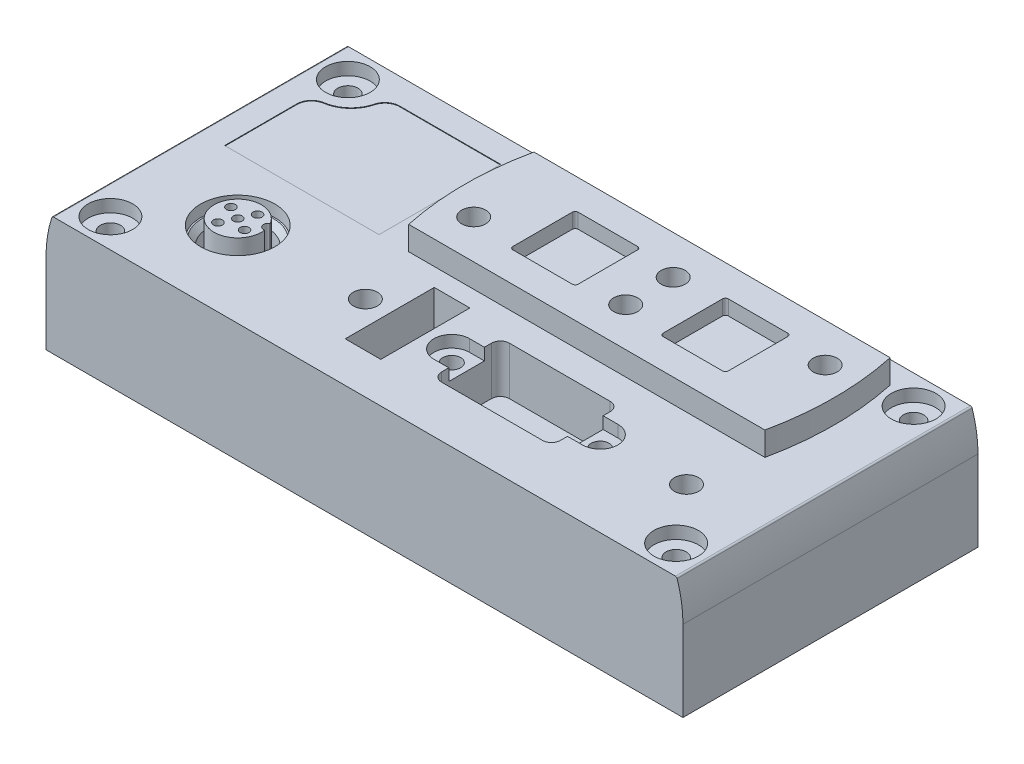
SolidWorks part; units mm, degrees
ref_plane "Front Plane" through (0, 0, 0) normal (0, 0, 1) x (1, 0, 0)
ref_plane "Top Plane" through (0, 0, 0) normal (0, 1, 0) x (1, 0, 0)
ref_plane "Right Plane" through (0, 0, 0) normal (1, 0, 0) x (0, 0, -1)
ref_plane "Plane1" through (0, 0, 0) normal (0, 0, 1) x (1, 0, 0)
sketch "Sketch1" plane through (0, 0, 0) normal (0, 0, 1) x (1, 0, 0)
  line L0 (-53.65, 13.6) -> (-53.65, 0)
  line L1 (-53.65, 0) -> (53.65, 0)
  line L2 (53.65, 0) -> (53.65, 13.6)
  line L3 (52.3818, 20) -> (-52.3818, 20)
  arc A0 (53.65, 13.6) -> (52.667, 19.7929) centre (33.65, 13.6) ccw
  arc A1 (52.667, 19.7929) -> (52.3818, 20) centre (52.3818, 19.7) ccw
  arc A2 (-52.3818, 20) -> (-52.667, 19.7929) centre (-52.3818, 19.7) ccw
  arc A3 (-52.667, 19.7929) -> (-53.65, 13.6) centre (-33.65, 13.6) ccw
extrude "Boss-Extrude1" add sketch "Sketch1" against normal blind 24.85 and the other way blind 24.85
ref_plane "Plane2" through (0, 0, 20) normal (0, 0, 1) x (1, 0, 0)
sketch "Sketch2" plane through (0, 0, 20) normal (0, 0, 1) x (1, 0, 0)
  line L0 (47.65, 20) -> (51.4, 20)
  line L1 (51.4, 20) -> (51.4, 17.9)
  line L2 (51.4, 17.9) -> (49.35, 17.9)
  line L3 (49.35, 17.9) -> (49.35, 12.7732)
  line L4 (49.35, 12.7732) -> (49.05, 12.6)
  line L5 (49.05, 12.6) -> (49.05, 12)
  line L6 (49.05, 12) -> (49.35, 12)
  line L7 (49.35, 12) -> (49.35, 0)
  line L8 (49.35, 0) -> (47.65, 0)
  line L9 (47.65, 0) -> (47.65, 20)
  line L10 (47.65, 0) -> (47.65, 20) construction
revolve "Cut-Revolve1" cut sketch "Sketch2" angle 360 about L10 reverse direction yes
ref_plane "Plane3" through (0, 0, -20) normal (0, 0, 1) x (1, 0, 0)
sketch "Sketch3" plane through (0, 0, -20) normal (0, 0, 1) x (1, 0, 0)
  line L0 (47.65, 20) -> (51.4, 20)
  line L1 (51.4, 20) -> (51.4, 17.9)
  line L2 (51.4, 17.9) -> (49.35, 17.9)
  line L3 (49.35, 17.9) -> (49.35, 12.7732)
  line L4 (49.35, 12.7732) -> (49.05, 12.6)
  line L5 (49.05, 12.6) -> (49.05, 12)
  line L6 (49.05, 12) -> (49.35, 12)
  line L7 (49.35, 12) -> (49.35, 0)
  line L8 (49.35, 0) -> (47.65, 0)
  line L9 (47.65, 0) -> (47.65, 20)
  line L10 (47.65, 0) -> (47.65, 20) construction
revolve "Cut-Revolve2" cut sketch "Sketch3" angle 360 about L10 reverse direction yes
ref_plane "Plane4" through (0, 0, -20) normal (0, 0, 1) x (1, 0, 0)
sketch "Sketch4" plane through (0, 0, -20) normal (0, 0, 1) x (1, 0, 0)
  line L0 (-47.65, 20) -> (-43.9, 20)
  line L1 (-43.9, 20) -> (-43.9, 17.9)
  line L2 (-43.9, 17.9) -> (-45.95, 17.9)
  line L3 (-45.95, 17.9) -> (-45.95, 12.7732)
  line L4 (-45.95, 12.7732) -> (-46.25, 12.6)
  line L5 (-46.25, 12.6) -> (-46.25, 12)
  line L6 (-46.25, 12) -> (-45.95, 12)
  line L7 (-45.95, 12) -> (-45.95, 0)
  line L8 (-45.95, 0) -> (-47.65, 0)
  line L9 (-47.65, 0) -> (-47.65, 20)
  line L10 (-47.65, 0) -> (-47.65, 20) construction
revolve "Cut-Revolve3" cut sketch "Sketch4" angle 360 about L10 reverse direction yes
ref_plane "Plane5" through (0, 0, 20) normal (0, 0, 1) x (1, 0, 0)
sketch "Sketch5" plane through (0, 0, 20) normal (0, 0, 1) x (1, 0, 0)
  line L0 (-47.65, 20) -> (-43.9, 20)
  line L1 (-43.9, 20) -> (-43.9, 17.9)
  line L2 (-43.9, 17.9) -> (-45.95, 17.9)
  line L3 (-45.95, 17.9) -> (-45.95, 12.7732)
  line L4 (-45.95, 12.7732) -> (-46.25, 12.6)
  line L5 (-46.25, 12.6) -> (-46.25, 12)
  line L6 (-46.25, 12) -> (-45.95, 12)
  line L7 (-45.95, 12) -> (-45.95, 0)
  line L8 (-45.95, 0) -> (-47.65, 0)
  line L9 (-47.65, 0) -> (-47.65, 20)
  line L10 (-47.65, 0) -> (-47.65, 20) construction
revolve "Cut-Revolve4" cut sketch "Sketch5" angle 360 about L10 reverse direction yes
ref_plane "Plane6" through (0, 0, 10.55) normal (0, 0, 1) x (1, 0, 0)
sketch "Sketch6" plane through (0, 0, 10.55) normal (0, 0, 1) x (1, 0, 0)
  line L0 (-35.65, 12.4) -> (-41.65, 12.4)
  line L1 (-41.65, 12.4) -> (-40.703, 13.347)
  line L2 (-40.703, 13.347) -> (-40.703, 17.053)
  line L3 (-40.703, 17.053) -> (-41.65, 18)
  line L4 (-41.65, 18) -> (-41.9, 18)
  line L5 (-41.9, 18) -> (-41.9, 20)
  line L6 (-41.9, 20) -> (-35.65, 20)
  line L7 (-35.65, 20) -> (-35.65, 12.4)
  line L8 (-35.65, 20) -> (-35.65, 12.4) construction
revolve "Cut-Revolve5" cut sketch "Sketch6" angle 360 about L8 reverse direction yes
cosmetic thread "Cosmetic Thread1" parameters "D1"=5.6, "D2"=12
ref_plane "Plane7" through (0, 21, 0) normal (0, 1, 0) x (1, 0, 0)
sketch "Sketch7" plane through (0, 21, 0) normal (0, 1, 0) x (1, 0, 0)
  arc A0 (-32.1775, -8.5646) -> (-31.6913, -9.9766) centre (-35.65, -10.55) ccw
  arc A1 (-31.6913, -9.9766) -> (-32.1775, -8.5646) centre (-31.8679, -9.2477) cw
  circle A2 centre (-33.403, -11.6459) radius 0.75
  circle A3 centre (-34.5541, -8.303) radius 0.75
  circle A4 centre (-35.65, -10.55) radius 0.75
  circle A5 centre (-36.7459, -12.797) radius 0.75
  circle A6 centre (-37.897, -9.4541) radius 0.75
extrude "Boss-Extrude2" add sketch "Sketch7" against normal blind 8.6
ref_plane "Plane8" through (0, 24, 0) normal (0, 1, 0) x (1, 0, 0)
sketch "Sketch8" plane through (0, 24, 0) normal (0, 1, 0) x (1, 0, 0)
  line L0 (-17.4, 0) -> (42.6, 0)
  line L1 (42.6, 21.1) -> (-17.4, 21.1)
  arc A0 (-17.4, 21.1) -> (-17.4, 0) centre (31.4743, 10.55) ccw
  arc A1 (42.6, 0) -> (42.6, 21.1) centre (-6.2743, 10.55) ccw
extrude "Boss-Extrude3" add sketch "Sketch8" against normal blind 4
ref_plane "Plane9" through (0, 24, 0) normal (0, 1, 0) x (1, 0, 0)
sketch "Sketch9" plane through (0, 24, 0) normal (0, 1, 0) x (1, 0, 0)
  circle A0 centre (-13, 6.55) radius 2.025
extrude "Cut-Extrude1" cut sketch "Sketch9" against normal blind 6.6
ref_plane "Plane10" through (0, 24, 0) normal (0, 1, 0) x (1, 0, 0)
sketch "Sketch10" plane through (0, 24, 0) normal (0, 1, 0) x (1, 0, 0)
  circle A0 centre (12.6, 14.55) radius 2.025
extrude "Cut-Extrude2" cut sketch "Sketch10" against normal blind 6.6
ref_plane "Plane11" through (0, 24, 0) normal (0, 1, 0) x (1, 0, 0)
sketch "Sketch11" plane through (0, 24, 0) normal (0, 1, 0) x (1, 0, 0)
  circle A0 centre (12.6, 6.55) radius 2.025
extrude "Cut-Extrude3" cut sketch "Sketch11" against normal blind 6.6
ref_plane "Plane12" through (0, 24, 0) normal (0, 1, 0) x (1, 0, 0)
sketch "Sketch12" plane through (0, 24, 0) normal (0, 1, 0) x (1, 0, 0)
  circle A0 centre (38.2, 14.55) radius 2.025
extrude "Cut-Extrude4" cut sketch "Sketch12" against normal blind 6.6
ref_plane "Plane13" through (0, 20, 0) normal (0, 1, 0) x (1, 0, 0)
sketch "Sketch13" plane through (0, 20, 0) normal (0, 1, 0) x (1, 0, 0)
  circle A0 centre (-14.15, -10.55) radius 2.025
extrude "Cut-Extrude5" cut sketch "Sketch13" against normal blind 6.6
ref_plane "Plane14" through (0, 20, 0) normal (0, 1, 0) x (1, 0, 0)
sketch "Sketch14" plane through (0, 20, 0) normal (0, 1, 0) x (1, 0, 0)
  circle A0 centre (39.95, -10.55) radius 2.025
extrude "Cut-Extrude6" cut sketch "Sketch14" against normal blind 6.6
ref_plane "Plane15" through (0, 20, 0) normal (0, 1, 0) x (1, 0, 0)
sketch "Sketch15" plane through (0, 20, 0) normal (0, 1, 0) x (1, 0, 0)
  line L0 (0.4, -13.55) -> (2.9, -13.55)
  line L1 (2.9, -13.55) -> (2.9, -14.55)
  line L2 (3.9, -15.55) -> (21.9, -15.55)
  line L3 (22.9, -14.55) -> (22.9, -13.55)
  line L4 (22.9, -13.55) -> (25.4, -13.55)
  line L5 (25.4, -7.55) -> (22.9, -7.55)
  line L6 (22.9, -7.55) -> (22.9, -6.55)
  line L7 (21.9, -5.55) -> (3.9, -5.55)
  line L8 (2.9, -6.55) -> (2.9, -7.55)
  line L9 (2.9, -7.55) -> (0.4, -7.55)
  arc A0 (0.4, -7.55) -> (0.4, -13.55) centre (0.4, -10.55) ccw
  arc A1 (2.9, -14.55) -> (3.9, -15.55) centre (3.9, -14.55) ccw
  arc A2 (21.9, -15.55) -> (22.9, -14.55) centre (21.9, -14.55) ccw
  arc A3 (25.4, -13.55) -> (25.4, -7.55) centre (25.4, -10.55) ccw
  arc A4 (22.9, -6.55) -> (21.9, -5.55) centre (21.9, -6.55) ccw
  arc A5 (3.9, -5.55) -> (2.9, -6.55) centre (3.9, -6.55) ccw
extrude "Cut-Extrude7" cut sketch "Sketch15" against normal blind 2
ref_plane "Plane16" through (0, 20, 0) normal (0, 1, 0) x (1, 0, 0)
sketch "Sketch16" plane through (0, 20, 0) normal (0, 1, 0) x (1, 0, 0)
  line L0 (2.9, -6.35) -> (2.9, -14.75)
  line L1 (4.4, -16.25) -> (21.4, -16.25)
  line L2 (22.9, -14.75) -> (22.9, -6.35)
  line L3 (21.4, -4.85) -> (4.4, -4.85)
  arc A0 (2.9, -14.75) -> (4.4, -16.25) centre (4.4, -14.75) ccw
  arc A1 (21.4, -16.25) -> (22.9, -14.75) centre (21.4, -14.75) ccw
  arc A2 (22.9, -6.35) -> (21.4, -4.85) centre (21.4, -6.35) ccw
  arc A3 (4.4, -4.85) -> (2.9, -6.35) centre (4.4, -6.35) ccw
extrude "Cut-Extrude8" cut sketch "Sketch16" against normal blind 8.1
ref_plane "Plane17" through (0, 20, 0) normal (0, 1, 0) x (1, 0, 0)
sketch "Sketch17" plane through (0, 20, 0) normal (0, 1, 0) x (1, 0, 0)
  circle A0 centre (25.4, -10.55) radius 1.5
extrude "Cut-Extrude9" cut sketch "Sketch17" against normal blind 5
ref_plane "Plane18" through (0, 20, 0) normal (0, 1, 0) x (1, 0, 0)
sketch "Sketch18" plane through (0, 20, 0) normal (0, 1, 0) x (1, 0, 0)
  circle A0 centre (0.4, -10.55) radius 1.5
extrude "Cut-Extrude10" cut sketch "Sketch18" against normal blind 5
ref_plane "Plane19" through (0, 24, 0) normal (0, 1, 0) x (1, 0, 0)
sketch "Sketch19" plane through (0, 24, 0) normal (0, 1, 0) x (1, 0, 0)
  line L0 (-5.4, 15.55) -> (-5.4, 5.55)
  line L1 (-4.9, 5.05) -> (5.1, 5.05)
  line L2 (5.6, 5.55) -> (5.6, 15.55)
  line L3 (5.1, 16.05) -> (-4.9, 16.05)
  arc A0 (-5.4, 5.55) -> (-4.9, 5.05) centre (-4.9, 5.55) ccw
  arc A1 (5.1, 5.05) -> (5.6, 5.55) centre (5.1, 5.55) ccw
  arc A2 (5.6, 15.55) -> (5.1, 16.05) centre (5.1, 15.55) ccw
  arc A3 (-4.9, 16.05) -> (-5.4, 15.55) centre (-4.9, 15.55) ccw
extrude "Cut-Extrude11" cut sketch "Sketch19" against normal blind 2.5
ref_plane "Plane20" through (0, 24, 0) normal (0, 1, 0) x (1, 0, 0)
sketch "Sketch20" plane through (0, 24, 0) normal (0, 1, 0) x (1, 0, 0)
  line L0 (19.9, 15.55) -> (19.9, 5.55)
  line L1 (20.4, 5.05) -> (30.4, 5.05)
  line L2 (30.9, 5.55) -> (30.9, 15.55)
  line L3 (30.4, 16.05) -> (20.4, 16.05)
  arc A0 (19.9, 5.55) -> (20.4, 5.05) centre (20.4, 5.55) ccw
  arc A1 (30.4, 5.05) -> (30.9, 5.55) centre (30.4, 5.55) ccw
  arc A2 (30.9, 15.55) -> (30.4, 16.05) centre (30.4, 15.55) ccw
  arc A3 (20.4, 16.05) -> (19.9, 15.55) centre (20.4, 15.55) ccw
extrude "Cut-Extrude12" cut sketch "Sketch20" against normal blind 2.5
ref_plane "Plane21" through (-10.05, 0, 0) normal (1, 0, 0) x (0, 0, -1)
sketch "Sketch21" plane through (-10.05, 0, 0) normal (1, 0, 0) x (0, 0, -1)
  line L0 (-18.05, 11.9) -> (-11.05, 11.9)
  line L1 (-11.05, 11.9) -> (-11.05, 12.9)
  line L2 (-11.05, 12.9) -> (-10.05, 12.9)
  line L3 (-10.05, 12.9) -> (-10.05, 11.9)
  line L4 (-10.05, 11.9) -> (-3.05, 11.9)
  line L5 (-3.05, 11.9) -> (-3.05, 20)
  line L6 (-3.05, 20) -> (-18.05, 20)
  line L7 (-18.05, 20) -> (-18.05, 11.9)
extrude "Cut-Extrude13" cut sketch "Sketch21" along normal blind 6
ref_plane "Plane22" through (0, 0, 0) normal (0, 1, 0) x (1, 0, 0)
sketch "Sketch22" plane through (0, 0, 0) normal (0, 1, 0) x (1, 0, 0)
  line L0 (-48.4, 12.1512) -> (-48.4, -12.1512)
  line L1 (-39.4234, -20.5) -> (40.208, -20.5)
  line L2 (48.4, -12.0497) -> (48.4, 12.0497)
  line L3 (40.208, 20.5) -> (-39.4234, 20.5)
  arc A0 (-48.4, -12.1512) -> (-46.2863, -14.6126) centre (-45.91, -12.1512) ccw
  arc A1 (-46.2863, -14.6126) -> (-41.8339, -18.6341) centre (-47.11, -20) cw
  arc A2 (-41.8339, -18.6341) -> (-39.4234, -20.5) centre (-39.4234, -18.01) ccw
  arc A3 (40.208, -20.5) -> (42.0607, -18.9391) centre (40.208, -18.62) ccw
  arc A4 (42.0607, -18.9391) -> (46.9131, -13.8882) centre (48.22, -20) cw
  arc A5 (46.9131, -13.8882) -> (48.4, -12.0497) centre (46.52, -12.0497) ccw
  arc A6 (48.4, 12.0497) -> (46.9131, 13.8882) centre (46.52, 12.0497) ccw
  arc A7 (46.9131, 13.8882) -> (42.0607, 18.9391) centre (48.22, 20) cw
  arc A8 (42.0607, 18.9391) -> (40.208, 20.5) centre (40.208, 18.62) ccw
  arc A9 (-39.4234, 20.5) -> (-41.8339, 18.6341) centre (-39.4234, 18.01) ccw
  arc A10 (-41.8339, 18.6341) -> (-46.2863, 14.6126) centre (-47.11, 20) cw
  arc A11 (-46.2863, 14.6126) -> (-48.4, 12.1512) centre (-45.91, 12.1512) ccw
extrude "Cut-Extrude14" cut sketch "Sketch22" along normal blind 10
ref_plane "Plane23" through (0, 0, 0) normal (0, 1, 0) x (1, 0, 0)
sketch "Sketch23" plane through (0, 0, 0) normal (0, 1, 0) x (1, 0, 0)
  line L0 (-48.4, 12.1512) -> (-48.4, 0)
  line L1 (-48.4, 0) -> (-22.4, 0)
  line L2 (-22.4, 0) -> (-22.4, 20.5)
  line L3 (-22.4, 20.5) -> (-39.4234, 20.5)
  arc A0 (-39.4234, 20.5) -> (-41.8339, 18.6341) centre (-39.4234, 18.01) ccw
  arc A1 (-41.8339, 18.6341) -> (-46.2863, 14.6126) centre (-47.11, 20) cw
  arc A2 (-46.2863, 14.6126) -> (-48.4, 12.1512) centre (-45.91, 12.1512) ccw
extrude "Cut-Extrude15" cut sketch "Sketch23" along normal blind 15
ref_plane "Plane24" through (0, 20, 0) normal (0, 1, 0) x (1, 0, 0)
sketch "Sketch24" plane through (0, 20, 0) normal (0, 1, 0) x (1, 0, 0)
  line L0 (-48.4, 12.1512) -> (-48.4, 0)
  line L1 (-48.4, 0) -> (-22.4, 0)
  line L2 (-22.4, 0) -> (-22.4, 20.5)
  line L3 (-22.4, 20.5) -> (-39.4234, 20.5)
  arc A0 (-39.4234, 20.5) -> (-41.8339, 18.6341) centre (-39.4234, 18.01) ccw
  arc A1 (-41.8339, 18.6341) -> (-46.2863, 14.6126) centre (-47.11, 20) cw
  arc A2 (-46.2863, 14.6126) -> (-48.4, 12.1512) centre (-45.91, 12.1512) ccw
extrude "Cut-Extrude16" cut sketch "Sketch24" against normal blind 0.1
